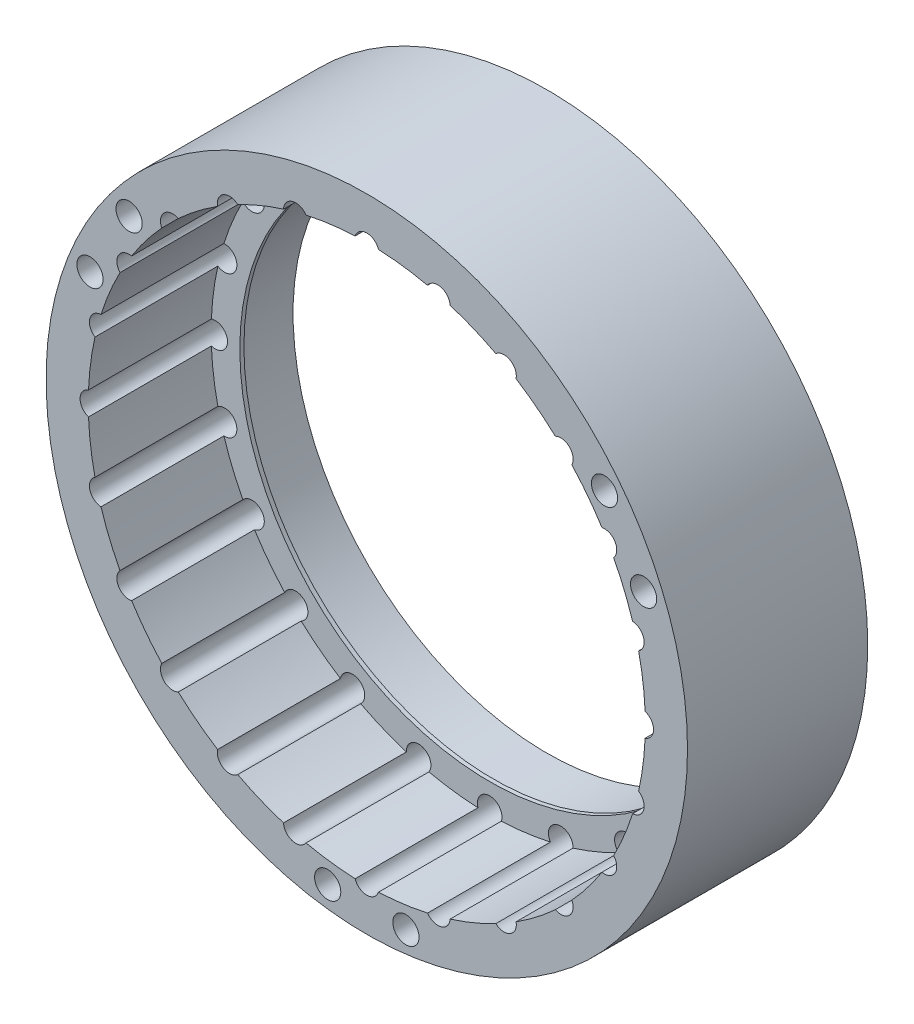
SolidWorks part; units mm, degrees
material "ABS"
ref_plane "Front Plane" through (0, 0, 0) normal (0, 0, 1) x (1, 0, 0)
ref_plane "Top Plane" through (0, 0, 0) normal (0, 1, 0) x (1, 0, 0)
ref_plane "Right Plane" through (0, 0, 0) normal (1, 0, 0) x (0, 0, -1)
sketch "CYC Master Sketch" plane through (0, 0, 0) normal (0, 0, 1) x (1, 0, 0)
  circle A0 centre (0, 0) radius 39.15
  circle A2 centre (0, 0) radius 33.5 construction
  circle A3 centre (-33.5, 0) radius 1.5
  circle A4 centre (-32.3585, 8.6704) radius 1.5
  circle A5 centre (-29.0119, 16.75) radius 1.5
  circle A6 centre (-23.6881, 23.6881) radius 1.5
  circle A7 centre (-16.75, 29.0119) radius 1.5
  circle A8 centre (-8.6704, 32.3585) radius 1.5
  circle A9 centre (0, 33.5) radius 1.5
  circle A10 centre (8.6704, 32.3585) radius 1.5
  circle A11 centre (16.75, 29.0119) radius 1.5
  circle A12 centre (23.6881, 23.6881) radius 1.5
  circle A13 centre (29.0119, 16.75) radius 1.5
  circle A14 centre (32.3585, 8.6704) radius 1.5
  circle A15 centre (33.5, 0) radius 1.5
  circle A16 centre (32.3585, -8.6704) radius 1.5
  circle A17 centre (29.0119, -16.75) radius 1.5
  circle A18 centre (23.6881, -23.6881) radius 1.5
  circle A19 centre (16.75, -29.0119) radius 1.5
  circle A20 centre (8.6704, -32.3585) radius 1.5
  circle A21 centre (0, -33.5) radius 1.5
  circle A22 centre (-8.6704, -32.3585) radius 1.5
  circle A23 centre (0, 0) radius 34
  circle A24 centre (-16.75, -29.0119) radius 1.5
  circle A25 centre (-23.6881, -23.6881) radius 1.5
  circle A26 centre (-29.0119, -16.75) radius 1.5
  circle A27 centre (-32.3585, -8.6704) radius 1.5
  circle A28 centre (0, 0) radius 31 construction
  circle A29 centre (0, 0) radius 25 construction
  circle A30 centre (0, 0) radius 36.575 construction
  circle A31 centre (4.774, -36.2621) radius 1.6
  circle A32 centre (-4.774, -36.2621) radius 1.6
  circle A33 centre (-33.7909, 13.9966) radius 1.6
  circle A34 centre (-29.0169, 22.2654) radius 1.6
  circle A35 centre (29.0169, 22.2654) radius 1.6
  circle A36 centre (33.7909, 13.9966) radius 1.6
  point P47 (0, 0)
  point P61 (-29.0119, 24.9173)
  point P62 (0, 0)
  point P72 (0, 0)
extrude "Gearbox Wall" add sketch "CYC Master Sketch" along normal blind 22 contours A0 A23 A13 A14 A15 A16 A17 A18 A19 A20 A21 A22 A3 A4 A5 A6 A7 A8 A9 A10 A11 A12 region at (-38.0427, 0, 0)
extrude "Gearbox Bottom" add sketch "CYC Master Sketch<3>" along normal blind 7 contours A21 A23 | A23 A20 | A20 A23 | A23 A19 | A19 A23 | A23 A18 | A18 A23 | A23 A17 | A17 A23 | A23 A16 | A16 A23 | A23 A15 | A15 A23 | A23 A14 | A14 A23 | A23 A13 | A13 A23 | A23 A12 | A12 A23 | A23 A11 | A11 A23 | A23 A10 | A10 A23 | A23 A9 | A9 A23 | A23 A8 | A8 A23 | A23 A7 | A7 A23 | A23 A6 | A6 A23 | A23 A5 | A5 A23 | A23 A4 | A4 A23 | A23 A3 | A3 A23 | A23 A22 | A22 A23 | A13 A23 A12 A11 A10 A9 A8 A7 A6 A5 A4 A3 A22 A21 A20 A19 A18 A17 A16 A15 A14 | A24 | A25 | A26 | A27 | A21 region at (-33.1184, 0, 0) region at (0, 0, 0) region at (-34.4085, 0, 0) region at (-31.99, 8.5717, 0) region at (-33.2361, 8.9056, 0) region at (-28.6814, 16.5592, 0) region at (-29.7987, 17.2043, 0) region at (-23.4183, 23.4183, 0) region at (-24.3305, 24.3305, 0) region at (-16.5592, 28.6814, 0) region at (-17.2043, 29.7987, 0) region at (-8.5717, 31.99, 0) region at (-8.9056, 33.2361, 0) region at (-8.9056, -33.2361, 0) region at (-8.5717, -31.99, 0) region at (0, 33.1184, 0) region at (0, 34.4085, 0) region at (0, -33.1184, 0) region at (8.5717, 31.99, 0) region at (8.9056, 33.2361, 0) region at (8.9056, -33.2361, 0) region at (8.5717, -31.99, 0) region at (16.5592, 28.6814, 0) region at (17.2043, 29.7987, 0) region at (17.2043, -29.7987, 0) region at (16.5592, -28.6814, 0) region at (23.4183, 23.4183, 0) region at (24.3305, 24.3305, 0) region at (24.3305, -24.3305, 0) region at (23.4183, -23.4183, 0) region at (28.6814, 16.5592, 0) region at (29.7987, 17.2043, 0) region at (29.7987, -17.2043, 0) region at (28.6814, -16.5592, 0) region at (31.99, 8.5717, 0) region at (33.2361, 8.9056, 0) region at (33.2361, -8.9056, 0) region at (31.99, -8.5717, 0) region at (33.1184, 0, 0) region at (34.4085, 0, 0)
sketch "CYC Master Sketch<3>" plane through (0, 0, 0) normal (0, 0, 1) x (1, 0, 0) same geometry as "CYC Master Sketch"
extrude "Pin Cut" cut sketch "CYC Master Sketch<2>" against normal blind 3 from surface contours A23 A7 | A7 A23 | A23 A6 | A6 A23 | A23 A5 | A5 A23 | A23 A4 | A4 A23 | A23 A3 | A3 A23 | A23 A22 | A22 A23 | A23 A21 | A21 A23 | A23 A20 | A20 A23 | A23 A19 | A19 A23 | A23 A18 | A18 A23 | A23 A17 | A17 A23 | A16 A23 | A23 A16 | A15 A23 | A23 A15 | A23 A14 | A14 A23 | A23 A13 | A13 A23 | A23 A12 | A12 A23 | A23 A11 | A11 A23 | A10 A23 | A23 A9 | A9 A23 | A23 A8 | A8 A23 | A23 A10 | A23 A24 | A23 A24 | A23 A25 | A23 A25 | A23 A26 | A23 A26 | A23 A27 | A23 A27 region at (-33.1184, 0, 0) region at (-34.4085, 0, 0) region at (-31.99, 8.5717, 0) region at (-33.2361, 8.9056, 0) region at (-31.99, -8.5717, 0) region at (-33.2361, -8.9056, 0) region at (-28.6814, 16.5592, 0) region at (-29.7987, 17.2043, 0) region at (-28.6814, -16.5592, 0) region at (-29.7987, -17.2043, 0) region at (-23.4183, 23.4183, 0) region at (-24.3305, 24.3305, 0) region at (-23.4183, -23.4183, 0) region at (-24.3305, -24.3305, 0) region at (-16.5592, 28.6814, 0) region at (-17.2043, 29.7987, 0) region at (-16.5592, -28.6814, 0) region at (-17.2043, -29.7987, 0) region at (-8.5717, 31.99, 0) region at (-8.9056, 33.2361, 0) region at (-8.9056, -33.2361, 0) region at (-8.5717, -31.99, 0) region at (0, 33.1184, 0) region at (0, 34.4085, 0) region at (0, -34.4085, 0) region at (0, -33.1184, 0) region at (8.5717, 31.99, 0) region at (8.9056, 33.2361, 0) region at (8.9056, -33.2361, 0) region at (8.5717, -31.99, 0) region at (16.5592, 28.6814, 0) region at (17.2043, 29.7987, 0) region at (17.2043, -29.7987, 0) region at (16.5592, -28.6814, 0) region at (23.4183, 23.4183, 0) region at (24.3305, 24.3305, 0) region at (24.3305, -24.3305, 0) region at (23.4183, -23.4183, 0) region at (28.6814, 16.5592, 0) region at (29.7987, 17.2043, 0) region at (29.7987, -17.2043, 0) region at (28.6814, -16.5592, 0) region at (31.99, 8.5717, 0) region at (33.2361, 8.9056, 0) region at (33.2361, -8.9056, 0) region at (31.99, -8.5717, 0) region at (33.1184, 0, 0) region at (34.4085, 0, 0) starting at face at (0, 0, 7)
sketch "CYC Master Sketch<2>" plane through (0, 0, 0) normal (0, 0, 1) x (1, 0, 0) same geometry as "CYC Master Sketch"
sketch "CYC Master" plane through (0, 0, 7) normal (0, 0, 1) x (1, 0, 0)
  circle A0 centre (0, 0) radius 39.15
  circle A2 centre (0, 0) radius 33.5 construction
  circle A3 centre (-33.5, 0) radius 1.5
  circle A4 centre (-32.3585, 8.6704) radius 1.5
  circle A5 centre (-29.0119, 16.75) radius 1.5
  circle A6 centre (-23.6881, 23.6881) radius 1.5
  circle A7 centre (-16.75, 29.0119) radius 1.5
  circle A8 centre (-8.6704, 32.3585) radius 1.5
  circle A9 centre (0, 33.5) radius 1.5
  circle A10 centre (8.6704, 32.3585) radius 1.5
  circle A11 centre (16.75, 29.0119) radius 1.5
  circle A12 centre (23.6881, 23.6881) radius 1.5
  circle A13 centre (29.0119, 16.75) radius 1.5
  circle A14 centre (32.3585, 8.6704) radius 1.5
  circle A15 centre (33.5, 0) radius 1.5
  circle A16 centre (32.3585, -8.6704) radius 1.5
  circle A17 centre (29.0119, -16.75) radius 1.5
  circle A18 centre (23.6881, -23.6881) radius 1.5
  circle A19 centre (16.75, -29.0119) radius 1.5
  circle A20 centre (8.6704, -32.3585) radius 1.5
  circle A21 centre (0, -33.5) radius 1.5
  circle A22 centre (-8.6704, -32.3585) radius 1.5
  circle A23 centre (0, 0) radius 34
  circle A24 centre (-16.75, -29.0119) radius 1.5
  circle A25 centre (-23.6881, -23.6881) radius 1.5
  circle A26 centre (-29.0119, -16.75) radius 1.5
  circle A27 centre (-32.3585, -8.6704) radius 1.5
  circle A28 centre (0, 0) radius 31 construction
  circle A29 centre (0, 0) radius 25 construction
  circle A30 centre (0, 0) radius 36.575 construction
  circle A31 centre (4.774, -36.2621) radius 1.6
  circle A32 centre (-4.774, -36.2621) radius 1.6
  circle A33 centre (-33.7909, 13.9966) radius 1.6
  circle A34 centre (-29.0169, 22.2654) radius 1.6
  circle A35 centre (29.0169, 22.2654) radius 1.6
  circle A36 centre (33.7909, 13.9966) radius 1.6
  point P47 (0, 0)
  point P61 (-29.0119, 24.9173)
  point P62 (0, 0)
  point P72 (0, 0)
sketch "Sketch2" plane through (0, 0, 7) normal (0, 0, 1) x (1, 0, 0)
  circle A0 centre (0, 0) radius 31
  circle A1 centre (0, 0) radius 31 construction
  point P3 (0, 0)
extrude "Housing Bearing Cut" cut sketch "Sketch2" against normal through all
sketch "Sketch3" plane through (0, 0, 7) normal (0, 0, 1) x (1, 0, 0)
  circle A0 centre (0, 0) radius 31
  circle A1 centre (0, 0) radius 30.5
  circle A2 centre (0, 0) radius 31 construction
  dimension "D1" = 61
  dimension "Housing Bearing Outer (Driven)" = 62
extrude "Housing Bearing Retainer" add sketch "Sketch3" against normal blind 0.5
equation "\"D1@Sketch3\" = \"Housing Bearing Outer (Driven)@Sketch3\" - 1"
